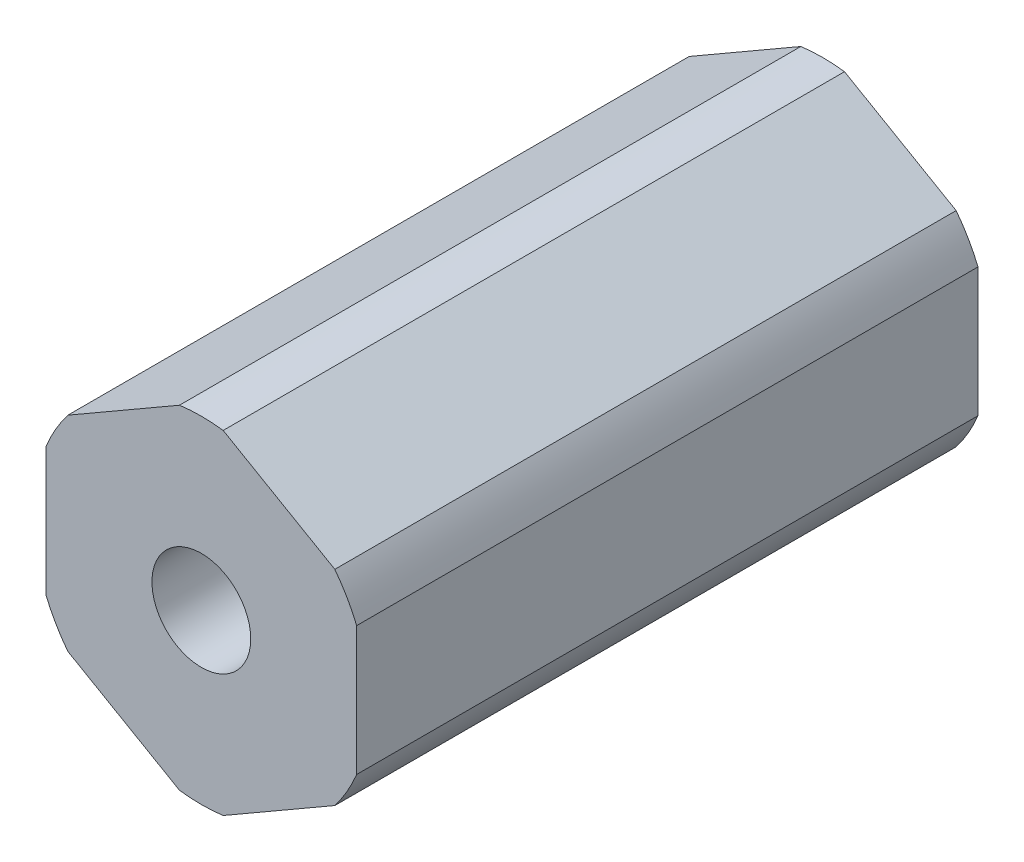
SolidWorks part; units mm, degrees
material "7075-T6 (SN)"
ref_plane "Front Plane" through (0, 0, 0) normal (0, 0, 1) x (1, 0, 0)
ref_plane "Top Plane" through (0, 0, 0) normal (0, 1, 0) x (1, 0, 0)
ref_plane "Right Plane" through (0, 0, 0) normal (1, 0, 0) x (0, 0, -1)
sketch "Sketch1" plane through (0, 0, 0) normal (0, 0, 1) x (1, 0, 0)
  line L1 (0, 7.3323) -> (-6.35, 3.6662)
  line L2 (-6.35, 3.6662) -> (-6.35, -3.6662)
  line L3 (-6.35, -3.6662) -> (0, -7.3323)
  line L4 (0, -7.3323) -> (6.35, -3.6662)
  line L5 (6.35, -3.6662) -> (6.35, 3.6662)
  line L6 (6.35, 3.6662) -> (0, 7.3323)
  circle A0 centre (0, 0) radius 6.35 construction
  circle A1 centre (0, 0) radius 6.875
  circle A2 centre (0, 0) radius 2.0193
  dimension "D1" = 12.7
  dimension "D2" = 4.0386
  dimension "D3" = 13.75
extrude "Boss-Extrude1" add sketch "Sketch1" along normal blind 25.4 contours L5 A1 L6 L1 L2 L3 L4 A2 region at (0, 6.6878, 0)
hole_wizard "#10-32 Tapped Hole1" positions "3DSketch2" profile "Sketch3" tap size "#10-32" standard "ANSI Inch"
sketch3d "3DSketch2"
  circle A0 centre (0, 0, 0) radius 2.0193 construction
  circle A1 centre (0, 0, 25.4) radius 2.0193 construction
  point P0 (0, 0, 25.4)
  point P2 (0, 0, 0)
  point P7 (0, 0, 2.0193)
  point P10 (0, 0, 27.4193)
sketch "Sketch3" plane through (0, 0, 25.4) normal (1, 0, 0) x (0, -1, 0)
  line L0 (0, 0) -> (0, 13.2428)
  line L1 (0, 13.2428) -> (2.0193, 12.0294)
  line L2 (2.0193, 12.0294) -> (2.0193, 0)
  line L5 (2.0193, 0) -> (0, 0)
  line L10 (0, 13.2428) -> (-2.0193, 12.0294) construction
  line L11 (0, -6.35) -> (0, 107.95) construction
  dimension "Tap Drill Dia." = 4.0386
  dimension "Tap Drill Depth" = 12.0294
  dimension "Drill Angle" = 118
cosmetic thread "Hole Thread1" parameters "D1"=9.652, "D2"=4.826
cosmetic thread "Hole Thread2" parameters "D1"=9.652, "D2"=4.826
equation "\"D3@Sketch1\"=13.75mm"
